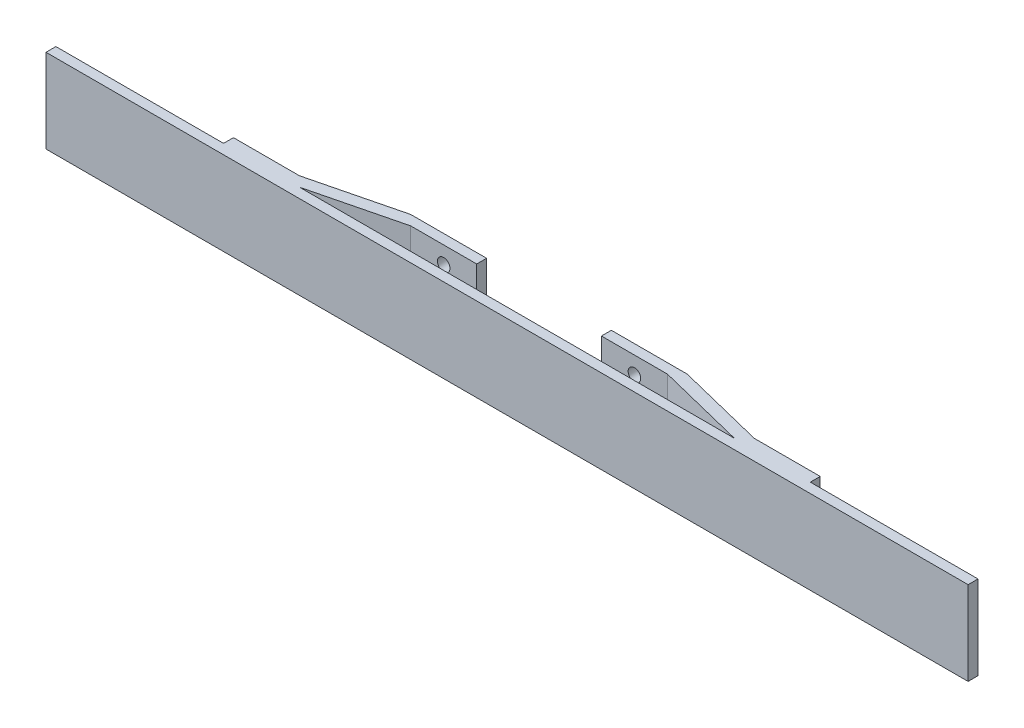
SolidWorks part; units mm, degrees
material "ABS"
ref_plane "Front Plane" through (0, 0, 0) normal (0, 0, 1) x (1, 0, 0)
ref_plane "Top Plane" through (0, 0, 0) normal (0, 1, 0) x (1, 0, 0)
ref_plane "Right Plane" through (0, 0, 0) normal (1, 0, 0) x (0, 0, -1)
sketch "Sketch1" plane through (0, 0, 0) normal (0, 0, 1) x (1, 0, 0)
  line L1 (-26.033, 10.5636) -> (278.767, 10.5636)
  line L2 (-26.033, 10.5636) -> (-26.033, -14.8364)
  line L3 (-26.033, -14.8364) -> (278.767, -14.8364)
  line L4 (278.767, 10.5636) -> (278.767, -14.8364)
  dimension "D1" = 25.4
  dimension "D2" = 304.8
extrude "Boss-Extrude2" add sketch "Sketch1" along normal blind 12.7 contours L1 L4 L3 L2
fillet "Fillet1" radius 12.7 2 edges at (-26.033, -2.1364, 12.7) (278.767, -2.1364, 12.7)
sketch "Sketch6" plane through (0, 10.5636, 0) normal (0, 1, 0) x (1, 0, 0)
  line L5 (-23.033, 0) -> (275.767, 0)
  line L6 (-13.333, -9.7) -> (266.067, -9.7)
  line L7 (-13.333, -9.7) -> (266.067, -9.7)
  arc A8 (266.067, -9.7) -> (275.767, 0) centre (266.067, 0) ccw
  arc A9 (-23.033, 0) -> (-13.333, -9.7) centre (-13.333, 0) ccw
  arc A10 (266.067, -9.7) -> (275.767, 0) centre (266.067, 0) ccw
  arc A11 (-23.033, 0) -> (-13.333, -9.7) centre (-13.333, 0) ccw
  dimension "D1" = 3
extrude "Cut-Extrude3" cut sketch "Sketch6" against normal through all
sketch "Sketch8" plane through (0, 0, 9.7) normal (0, 0, -1) x (-1, 0, 0)
  line L0 (13.333, 10.5636) -> (-266.067, 10.5636) construction
  line L1 (-145.267, 10.5636) -> (-215.267, 10.5636)
  line L2 (-145.267, 10.5636) -> (-145.267, -14.8364)
  line L3 (-145.267, -14.8364) -> (-215.267, -14.8364)
  line L4 (-215.267, 10.5636) -> (-215.267, -14.8364)
  line L5 (13.333, -14.8364) -> (-266.067, -14.8364) construction
  line L6 (-266.067, -14.8364) -> (-266.067, 10.5636) construction
  line L7 (-37.467, 10.5636) -> (-107.467, 10.5636)
  line L8 (-37.467, 10.5636) -> (-37.467, -14.8364)
  line L9 (-37.467, -14.8364) -> (-107.467, -14.8364)
  line L10 (-107.467, 10.5636) -> (-107.467, -14.8364)
  line L11 (13.333, -14.8364) -> (13.333, 10.5636) construction
  dimension "D1" = 50.8
  dimension "D2" = 70
  dimension "D3" = 50.8
  dimension "D4" = 70
extrude "Boss-Extrude3" add sketch "Sketch8" along normal blind 9.7
sketch "Sketch9" plane through (0, 10.5636, 0) normal (0, 1, 0) x (1, 0, 0)
  line L0 (145.267, -9.7) -> (165.267, -9.7)
  line L1 (165.267, -9.7) -> (192.267, -9.7)
  line L2 (192.267, -9.7) -> (165.267, -3)
  line L3 (165.267, -3) -> (145.267, -3)
  line L4 (145.267, 0) -> (145.267, -9.7) construction
  line L5 (145.267, -3) -> (145.267, -9.7)
  line L6 (145.267, 0) -> (215.267, 0) construction
  line L7 (215.267, -6.7) -> (195.267, -6.7)
  line L8 (215.267, 0) -> (215.267, -9.7) construction
  line L9 (195.267, -6.7) -> (168.267, 0)
  line L10 (168.267, 0) -> (215.267, 0)
  line L11 (215.267, 0) -> (215.267, -6.7)
  dimension "D1" = 3
  dimension "D2" = 20
  dimension "D3" = 27
  dimension "D4" = 20
  dimension "D5" = 20
  dimension "D6" = 3
  dimension "D7" = 47
extrude "Cut-Extrude4" cut sketch "Sketch9" against normal through all
sketch "Sketch12" plane through (0, 10.5636, 0) normal (0, 1, 0) x (1, 0, 0)
  line L0 (107.467, -9.7) -> (107.467, -3)
  line L1 (107.467, 0) -> (107.467, -9.7) construction
  line L2 (107.467, -3) -> (87.467, -3)
  line L3 (87.467, -3) -> (60.467, -9.7)
  line L4 (60.467, -9.7) -> (107.467, -9.7)
  line L11 (37.467, -6.7) -> (57.467, -6.7)
  line L12 (37.467, 0) -> (37.467, -9.7) construction
  line L13 (57.467, -6.7) -> (84.467, 0)
  line L14 (37.467, 0) -> (107.467, 0) construction
  line L15 (84.467, 0) -> (37.467, 0)
  line L16 (37.467, 0) -> (37.467, -6.7)
  dimension "D1" = 3
  dimension "D2" = 20
  dimension "D3" = 47
  dimension "D4" = 3
  dimension "D5" = 20
  dimension "D6" = 47
extrude "Cut-Extrude5" cut sketch "Sketch12" against normal through all
sketch "Sketch13" plane through (0, 0, 12.7) normal (0, 0, 1) x (1, 0, 0)
  line L1 (-13.333, -14.8364) -> (-26.033, -14.8364)
  line L2 (-13.333, -14.8364) -> (-13.333, 10.5636)
  line L3 (-13.333, 10.5636) -> (-26.033, 10.5636)
  line L4 (-26.033, -14.8364) -> (-26.033, 10.5636)
  line L5 (266.067, -14.8364) -> (278.767, -14.8364)
  line L6 (266.067, -14.8364) -> (266.067, 10.5636)
  line L7 (266.067, 10.5636) -> (278.767, 10.5636)
  line L8 (278.767, -14.8364) -> (278.767, 10.5636)
extrude "Cut-Extrude7" cut sketch "Sketch13" against normal through all
sketch "Sketch14" plane through (0, 0, 3) normal (0, 0, 1) x (1, 0, 0)
  line L0 (97.467, -14.8364) -> (97.467, 10.5636) construction
  line L1 (107.467, -14.8364) -> (87.467, -14.8364) construction
  line L2 (107.467, 10.5636) -> (87.467, 10.5636) construction
  line L3 (107.467, -2.1364) -> (87.467, -2.1364) construction
  line L4 (107.467, -14.8364) -> (107.467, 10.5636) construction
  line L5 (87.467, -14.8364) -> (87.467, 10.5636) construction
  point P12 (97.467, 5.3636)
  point P13 (97.467, -9.6364)
  dimension "D1" = 7.5
hole_wizard "#6 Clearance Hole1" positions "Sketch15" profile "Sketch16" hole size "#6" standard "ANSI Inch" end condition up to next
sketch "Sketch15" plane through (0, 0, 3) normal (0, 0, 1) x (1, 0, 0)
  line L0 (107.467, -2.1364) -> (145.267, -2.1364) construction
  line L1 (145.267, -14.8364) -> (145.267, 10.5636) construction
  line L3 (126.367, -2.1364) -> (126.367, 16.7203) construction
  point P0 (97.467, 5.3636)
  point P2 (97.467, -9.6364)
  point P22 (155.267, -9.6364)
  point P23 (155.267, 5.3636)
sketch "Sketch16" plane through (97.467, 5.3636, 3) normal (1, 0, 0) x (0, -1, 0)
  line L0 (0, 0) -> (0, 3)
  line L1 (0, 3) -> (1.8986, 3)
  line L2 (1.8986, 3) -> (1.8986, 0)
  line L5 (1.8986, 0) -> (0, 0)
  line L11 (0, -6.35) -> (0, 107.95) construction
  dimension "Thru Hole Dia." = 3.7973
  dimension "Thru Hole Depth" = 3
